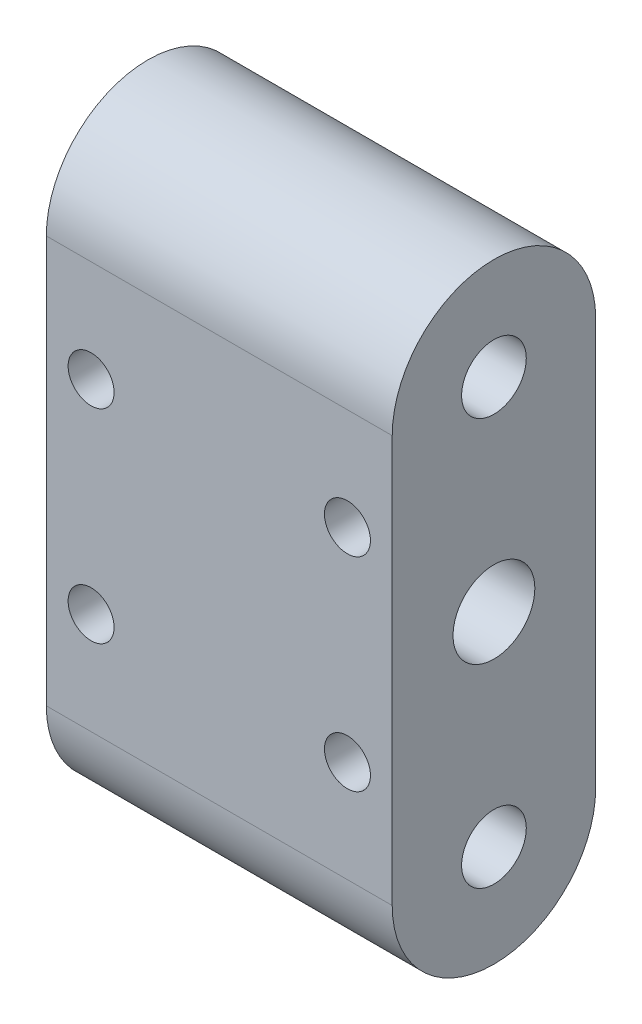
SolidWorks part; units mm, degrees
ref_plane "Front" through (0, 0, 0) normal (0, 0, 1) x (1, 0, 0)
ref_plane "Top" through (0, 0, 0) normal (0, 1, 0) x (1, 0, 0)
ref_plane "Right" through (0, 0, 0) normal (1, 0, 0) x (0, 0, -1)
sketch "Sketch1" plane through (0, 0, 0) normal (1, 0, 0) x (0, 0, -1)
  line L0 (0, 12.7) -> (0, -12.7) construction
  line L1 (6.35, 12.7) -> (6.35, -12.7)
  line L2 (-6.35, 12.7) -> (-6.35, -12.7)
  arc A0 (6.35, 12.7) -> (-6.35, 12.7) centre (0, 12.7) ccw
  arc A1 (-6.35, -12.7) -> (6.35, -12.7) centre (0, -12.7) ccw
  point P2 (0, 0)
  dimension "D1" = 12.7
  dimension "D2" = 25.4
extrude "Boss-Extrude1" add sketch "Sketch1" along normal blind 21.59
hole_wizard "1/4-20 Tapped Hole1" positions "Sketch2" profile "Sketch3" tap size "1/4-20" standard "ANSI Inch" end condition through all
sketch "Sketch2" plane through (21.59, 0, 0) normal (1, 0, 0) x (0, 0, -1)
  point P0 (0, 0)
sketch "Sketch3" plane through (21.59, 0, 0) normal (0, 1, 0) x (0, 0, -1)
  line L0 (0, 0) -> (0, 21.59)
  line L1 (0, 21.59) -> (2.5527, 21.59)
  line L2 (2.5527, 21.59) -> (2.5527, 0)
  line L5 (2.5527, 0) -> (0, 0)
  line L11 (0, -6.35) -> (0, 107.95) construction
  dimension "Thru Tap Drill Dia." = 5.1054
  dimension "Thru Tap Drill Depth" = 21.59
cosmetic thread "Hole Thread1" parameters "D2"=6.35
hole_wizard "#10-32 Tapped Hole1" positions "Sketch4" profile "Sketch5" tap size "#10-32" standard "ANSI Inch" end condition through all
sketch "Sketch4" plane through (21.59, 0, 0) normal (1, 0, 0) x (0, 0, -1)
  point P0 (0, 12.7)
  point P2 (0, -12.7)
sketch "Sketch5" plane through (21.59, 12.7, 0) normal (0, 1, 0) x (0, 0, -1)
  line L0 (0, 0) -> (0, 21.59)
  line L1 (0, 21.59) -> (2.0193, 21.59)
  line L2 (2.0193, 21.59) -> (2.0193, 0)
  line L5 (2.0193, 0) -> (0, 0)
  line L11 (0, -6.35) -> (0, 107.95) construction
  dimension "Thru Tap Drill Dia." = 4.0386
  dimension "Thru Tap Drill Depth" = 21.59
cosmetic thread "Hole Thread2" parameters "D2"=4.826
cosmetic thread "Hole Thread3" parameters "D2"=4.826
hole_wizard "#6-40 Tapped Hole1" positions "Sketch6" profile "Sketch7" tap size "#6-40" standard "ANSI Inch" end condition through all
sketch "Sketch6" plane through (0, 0, 6.35) normal (0, 0, 1) x (1, 0, 0)
  line L5 (2.795, 6.35) -> (2.795, -6.35) construction
  line L7 (0, 0) -> (21.59, 0) construction
  line L8 (0, 12.7) -> (0, -12.7) construction
  line L9 (21.59, 12.7) -> (21.59, -12.7) construction
  line L12 (2.795, 6.35) -> (18.795, 6.35) construction
  line L14 (10.795, 6.35) -> (10.795, 0) construction
  point P0 (2.795, 6.35)
  point P2 (18.795, 6.35)
  point P4 (2.795, -6.35)
  point P6 (18.795, -6.35)
  point P54 (2.795, 0)
  dimension "D1" = 16
  dimension "D2" = 12.7
cosmetic thread "Hole Thread4" parameters "D2"=3.5052
cosmetic thread "Hole Thread5" parameters "D2"=3.5052
cosmetic thread "Hole Thread6" parameters "D2"=3.5052
cosmetic thread "Hole Thread7" parameters "D2"=3.5052
sketch "Sketch7" plane through (2.795, 6.35, 6.35) normal (1, 0, 0) x (0, -1, 0)
  line L0 (0, 0) -> (0, 12.7)
  line L1 (0, 12.7) -> (1.4351, 12.7)
  line L2 (1.4351, 12.7) -> (1.4351, 0)
  line L5 (1.4351, 0) -> (0, 0)
  line L11 (0, -6.35) -> (0, 107.95) construction
  dimension "Thru Tap Drill Dia." = 2.8702
  dimension "Thru Tap Drill Depth" = 12.7
